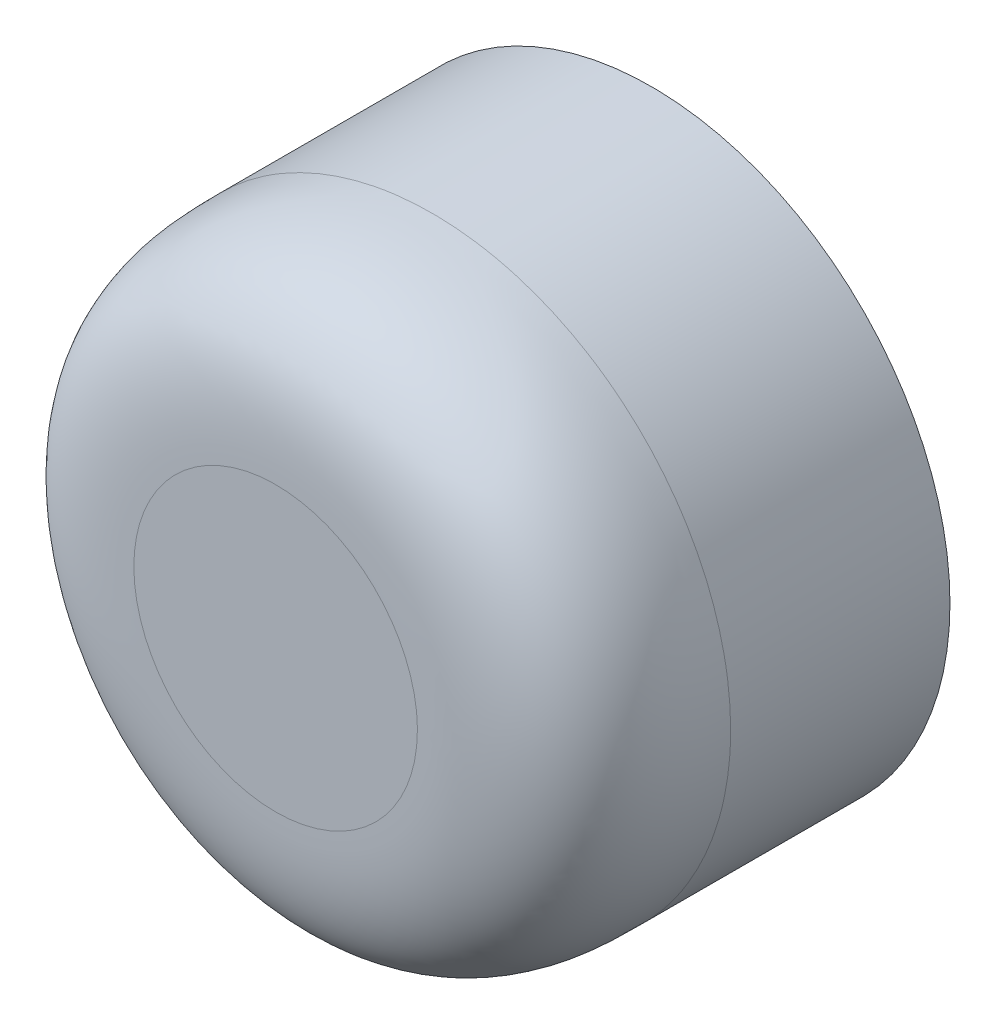
SolidWorks part; units mm, degrees
ref_plane "Front" through (0, 0, 0) normal (0, 0, 1) x (1, 0, 0)
ref_plane "Top" through (0, 0, 0) normal (0, 1, 0) x (1, 0, 0)
ref_plane "Right" through (0, 0, 0) normal (1, 0, 0) x (0, 0, -1)
sketch "Sketch1" plane through (0, 0, 0) normal (0, 0, 1) x (1, 0, 0)
  circle A0 centre (0, 0) radius 9.525
  dimension "D1" = 19.05
extrude "Boss-Extrude1" add sketch "Sketch1" along normal blind 12
fillet "Fillet1" radius 5 1 edges at (9.525, 0, 12) curvature continuous yes
